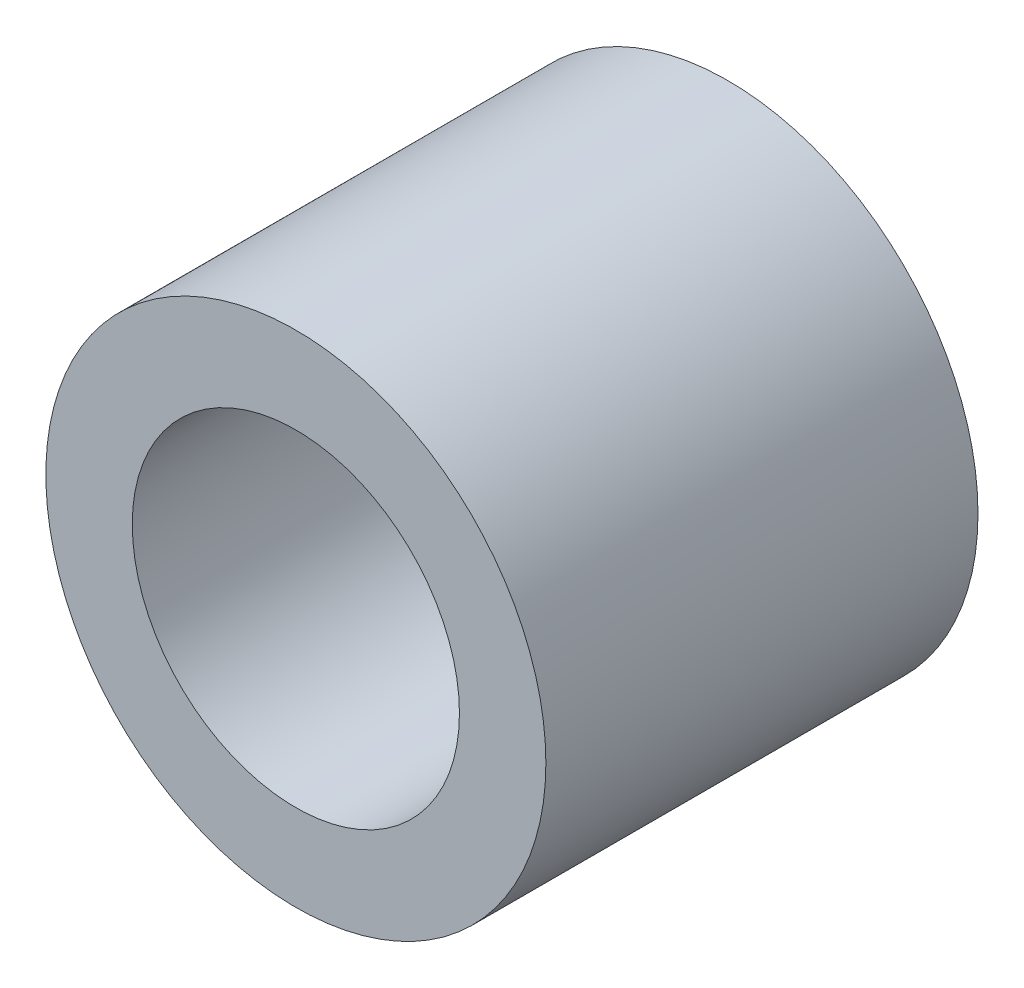
SolidWorks part; units mm, degrees
ref_plane "Top Plane" through (0, 0, 0) normal (0, 0, 1) x (1, 0, 0)
ref_plane "Right Plane" through (0, 0, 0) normal (0, 1, 0) x (1, 0, 0)
ref_plane "Front Plane" through (0, 0, 0) normal (1, 0, 0) x (0, 0, -1)
ref_axis "x-axis" through (-88.99, 0, 0) along (1, 0, 0)
ref_axis "y-axis" through (0, -55, 0) along (0, 1, 0)
ref_axis "z-axis" through (0, 0, 55) along (0, 0, -1)
sketch "Sketch1" plane through (0, 0, 0) normal (0, 0, 1) x (1, 0, 0)
  circle A0 centre (0, 0) radius 4.05
  dimension "D1" = 8.1
extrude "Boss-Extrude1" add sketch "Sketch1" along normal blind 7
hole_wizard "M5 Clearance Hole1" positions "Sketch2" profile "Sketch3" hole size "M5" standard "ANSI Metric" end condition through all
sketch "Sketch2" plane through (0, 0, 7) normal (0, 0, 1) x (1, 0, 0)
  point P0 (0, 0)
sketch "Sketch3" plane through (0, 0, 7) normal (1, 0, 0) x (0, -1, 0)
  line L0 (0, 0) -> (0, 7)
  line L1 (0, 7) -> (2.65, 7)
  line L2 (2.65, 7) -> (2.65, 0)
  line L5 (2.65, 0) -> (0, 0)
  line L11 (0, -6.35) -> (0, 107.95) construction
  dimension "Thru Hole Dia." = 5.3
  dimension "Thru Hole Depth" = 7
